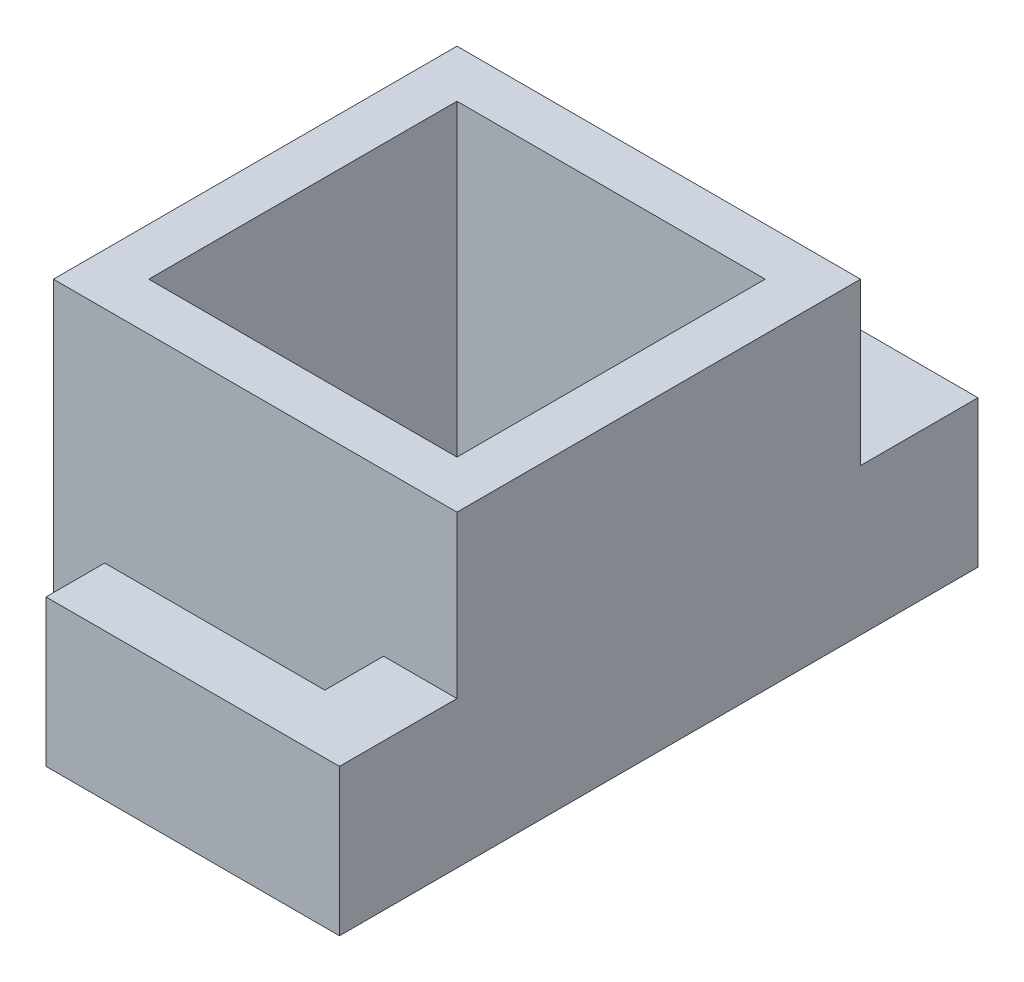
SolidWorks part; units mm, degrees
ref_plane "Front Plane" through (0, 0, 0) normal (0, 0, 1) x (1, 0, 0)
ref_plane "Top Plane" through (0, 0, 0) normal (0, 1, 0) x (1, 0, 0)
ref_plane "Right Plane" through (0, 0, 0) normal (1, 0, 0) x (0, 0, -1)
sketch "Sketch1" plane through (0, 0, 0) normal (0, 1, 0) x (1, 0, 0)
  line L1 (0, 0) -> (42, 0)
  line L2 (0, 0) -> (0, 42)
  line L3 (0, 42) -> (42, 42)
  line L4 (42, 0) -> (42, 42)
  line L5 (-6.5, -6.5) -> (48.5, -6.5)
  line L6 (-6.5, -6.5) -> (-6.5, 48.5)
  line L7 (-6.5, 48.5) -> (48.5, 48.5)
  line L8 (48.5, -6.5) -> (48.5, 48.5)
  dimension "D1" = 55
  dimension "D2" = 55
  dimension "D3" = 42
  dimension "D4" = 42
  dimension "D5" = 6.5
  dimension "D6" = 6.5
extrude "Boss-Extrude1" add sketch "Sketch1" along normal blind 42
sketch "Sketch2" plane through (0, 0, 0) normal (0, -1, 0) x (1, 0, 0)
  line L0 (38.5, 6.5) -> (38.5, 14.51)
  line L1 (-6.5, 6.5) -> (48.5, 6.5) construction
  line L2 (38.5, 14.51) -> (8.5, 14.51)
  line L3 (8.5, 14.51) -> (8.5, 22.51)
  line L4 (8.5, 22.51) -> (48.5, 22.51)
  line L5 (48.5, 22.51) -> (48.5, 6.5)
  line L6 (-6.5, -21) -> (48.5, -21) construction
  line L9 (-6.5, -48.5) -> (-6.5, 6.5) construction
  line L10 (8.5, -56.51) -> (8.5, -64.51)
  line L11 (8.5, -64.51) -> (48.5, -64.51)
  line L12 (38.5, -56.51) -> (8.5, -56.51)
  line L13 (38.5, -48.5) -> (38.5, -56.51)
  line L14 (48.5, -64.51) -> (48.5, -48.5)
  line L15 (48.5, -48.5) -> (38.5, -48.5)
  line L16 (48.5, 6.5) -> (38.5, 6.5)
  point P12 (-6.5, -21)
  dimension "D1" = 8.01
  dimension "D2" = 8
  dimension "D3" = 40
  dimension "D4" = 10
extrude "Boss-Extrude2" add sketch "Sketch2" against normal blind 20
